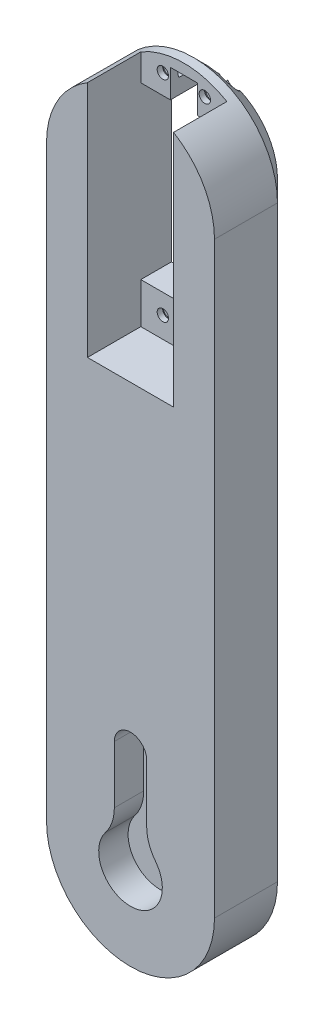
SolidWorks part; units mm, degrees
ref_plane "Front Plane" through (0, 0, 0) normal (0, 0, 1) x (1, 0, 0)
ref_plane "Top Plane" through (0, 0, 0) normal (0, 1, 0) x (1, 0, 0)
ref_plane "Right Plane" through (0, 0, 0) normal (1, 0, 0) x (0, 0, -1)
sketch "Sketch1" plane through (0, 0, 0) normal (0, 0, 1) x (1, 0, 0)
  line L0 (0, 0) -> (0, 147.804) construction
  line L4 (0, 140) -> (0, 0) construction
  line L6 (20, 140) -> (20, 0)
  line L7 (-20, 140) -> (-20, 0)
  arc A1 (20, 140) -> (-20, 140) centre (0, 140) ccw
  arc A2 (-20, 0) -> (20, 0) centre (0, 0) ccw
  point P2 (0, -30.875)
  point P7 (0, 70)
  dimension "D1" = 140
  dimension "D3" = 40
extrude "Boss-Extrude1" add sketch "Sketch1" along normal mid plane 20
chamfer "Chamfer1" distance 5 angle 45 4 edges at (-20, 70, -10) (0, -20, -10) (20, 70, -10) (0, 160, -10)
sketch "Sketch3" plane through (0, 0, 0) normal (1, 0, 0) x (0, 0, -1)
  line L0 (-10, 130.5) -> (29.3, 130.5) construction
  line L1 (29.3, 111.5) -> (29.3, 149.5) construction
  line L2 (2.7, 150.79) -> (2.7, 160.5)
  line L3 (2.7, 160.5) -> (-10, 160.5)
  line L4 (10, 140) -> (10, 0) construction
  line L5 (2.7, 150.79) -> (10, 150.79)
  line L7 (10, 150.79) -> (10, 130.5)
  line L8 (-10, 0) -> (-10, 140) construction
  line L9 (10, 130.5) -> (-10, 130.5)
  line L10 (10, 0) -> (10, 140) construction
  line L11 (-10, 130.5) -> (-10, 160.5)
  dimension "D1" = 20.29
  dimension "D2" = 30
  dimension "D3" = 12.7
extrude "Cut-Extrude1" cut sketch "Sketch3" against normal mid plane 20.5
ref_axis "Axis1" through (-6, 155.5, -2.3404) along (0, 0, 1)
sketch "Sketch10" plane through (0, 0, -2.7) normal (0, 0, 1) x (1, 0, 0)
  line L0 (8.25, 155.5) -> (-8.25, 155.5) construction
  arc A0 (4.4736, 157.1531) -> (7.6279, 157.0532) centre (6, 155.5) ccw construction
  arc A1 (-7.6279, 157.0532) -> (-4.4736, 157.1531) centre (-6, 155.5) ccw construction
  circle A2 centre (-5, 155.5) radius 2
  dimension "D1" = 4
  dimension "D2" = 1
ref_plane "Plane1" through (-5, 0, 0) normal (1, 0, 0) x (0, 0, -1)
sketch "Sketch4" plane through (-5, 0, 0) normal (1, 0, 0) x (0, 0, -1)
  line L0 (2.3404, 155.5) -> (-2.1596, 155.5) construction
  line L1 (2.7, 155.5) -> (10, 155.5)
  line L2 (2.7, 150.79) -> (2.7, 157.1737) construction
  line L3 (2.7, 155.5) -> (2.7, 156.85)
  line L4 (2.7, 156.85) -> (4, 156.85)
  line L5 (4, 156.85) -> (4.75, 157.6)
  line L6 (4.75, 157.6) -> (10, 157.6)
  line L7 (10, 157.6) -> (10, 155.5)
  line L8 (10, 140) -> (10, 155) construction
  dimension "D1" = 6
  dimension "D2" = 1.35
  dimension "D3" = 2.1
  dimension "D4" = 135
revolve "Cut-Revolve1" cut sketch "Sketch4" angle 360 about L1
ref_plane "Plane2" through (0, 0, 0) normal (1, 0, 0) x (0, 0, -1)
mirror "Mirror1" about plane through (0, 0, 0) normal (1, 0, 0) of "Cut-Revolve1"
mirror "Mirror2" about plane through (-10.25, 130.5, -10) normal (0, -1, 0) of "Mirror1", "Cut-Extrude1"
sketch "Sketch5" plane through (0, 0, -2.7) normal (0, 0, 1) x (1, 0, 0)
  line L0 (-10.25, 150.79) -> (10.25, 150.79) construction
  line L1 (-3.2, 150.79) -> (3.2, 150.79)
  line L2 (-3.2, 150.79) -> (-3.2, 157.5)
  line L3 (-3.2, 157.5) -> (3.2, 157.5)
  line L4 (3.2, 150.79) -> (3.2, 157.5)
  line L5 (4.3379, 157.5) -> (-4.3379, 157.5) construction
  line L7 (3.2, 147.5) -> (3.2, 142.5) construction
  line L8 (-3.2, 147.5) -> (-3.2, 142.5) construction
extrude "Cut-Extrude2" cut sketch "Sketch5" against normal blind 24
sketch "Sketch6" plane through (0, 0, 10) normal (0, 0, 1) x (1, 0, 0)
  line L0 (0, 0) -> (0, 24.5) construction
  line L1 (-3.85, 10.8193) -> (-3.85, 24.5)
  line L2 (3.85, 10.8193) -> (3.85, 24.5)
  arc A0 (-5.9695, 4.6632) -> (5.9695, 4.6632) centre (0, 0) ccw
  arc A2 (3.85, 24.5) -> (-3.85, 24.5) centre (0, 24.5) ccw
  arc A3 (-3.85, 10.8193) -> (-5.9695, 4.6632) centre (-13.85, 10.8193) cw
  arc A4 (3.85, 10.8193) -> (5.9695, 4.6632) centre (13.85, 10.8193) ccw
  point P3 (0, 12.25)
  dimension "D1" = 15.15
  dimension "D3" = 3.85
  dimension "D4" = 10
  dimension "D2" = 24.5
extrude "Cut-Extrude3" cut sketch "Sketch6" against normal blind 7
sketch "Sketch9" plane through (0, 0, -10) normal (0, 0, -1) x (-1, 0, 0)
  line L0 (0, -20) -> (0, 58.9157) construction
  line L1 (10.25, 100.5) -> (-10.25, 100.5) construction
  line L2 (-5, -21) -> (5, -21)
  line L3 (-5, -21) -> (-5, 97.5)
  line L4 (-5, 97.5) -> (5, 97.5)
  line L5 (5, -21) -> (5, 97.5)
  line L6 (-5, -21) -> (5, 97.5) construction
  line L7 (-5, 97.5) -> (5, -21) construction
  arc A0 (-20, 0) -> (20, 0) centre (0, 0) ccw construction
  point P7 (0, 38.25)
  dimension "D1" = 3
  dimension "D2" = 1
  dimension "D3" = 10
extrude "Cut-Extrude6" cut sketch "Sketch9" against normal blind 11
chamfer "Chamfer2" distance 5 angle 45 2 edges at (5, 39.0675, 1) (-5, 39.0675, 1)
sketch "Sketch7" plane through (0, 0, -10) normal (0, 0, -1) x (-1, 0, 0)
  circle A0 centre (0, 0) radius 4
  circle A1 centre (0, 24.5) radius 4
  dimension "D1" = 8
extrude "Cut-Extrude4" cut sketch "Sketch7" against normal blind 11
sketch "Sketch8" plane through (0, 0, 1) normal (0, 0, -1) x (-1, 0, 0)
  circle A0 centre (0, 24.5) radius 1.6
  circle A1 centre (0, 0) radius 1.6
  dimension "D1" = 3.2
extrude "Cut-Extrude5" cut sketch "Sketch8" against normal blind 11
